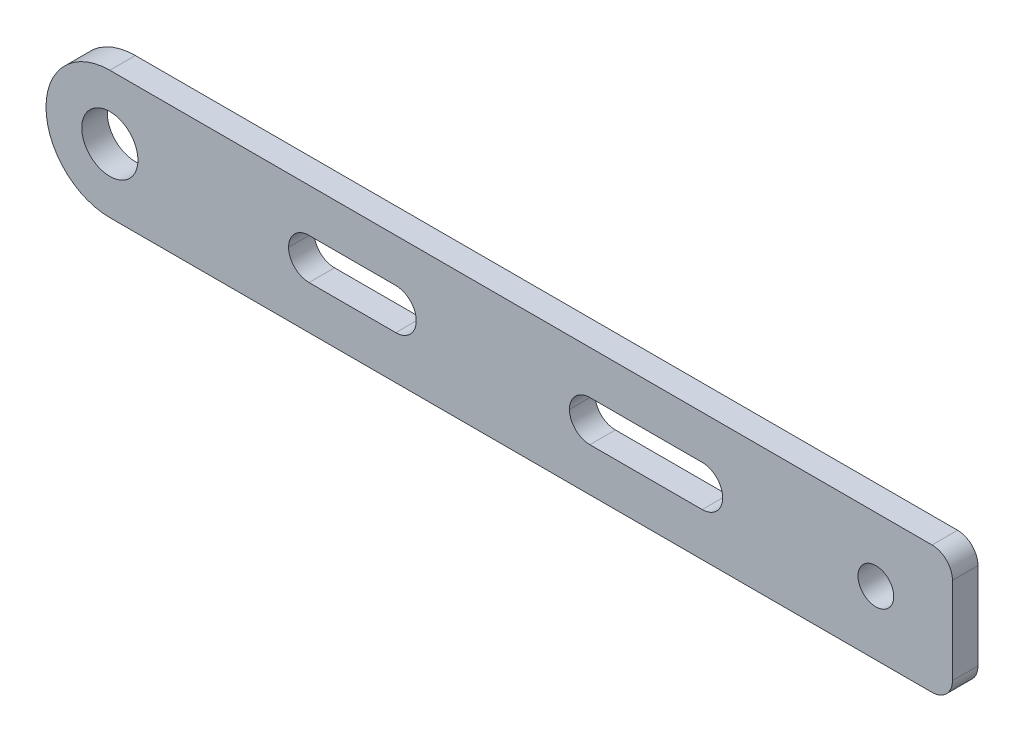
SolidWorks part; units mm, degrees
ref_plane "Front Plane" through (0, 0, 0) normal (0, 0, 1) x (1, 0, 0)
ref_plane "Top Plane" through (0, 0, 0) normal (0, 1, 0) x (1, 0, 0)
ref_plane "Right Plane" through (0, 0, 0) normal (1, 0, 0) x (0, 0, -1)
sketch "Sketch1" plane through (0, 0, 0) normal (0, 0, 1) x (1, 0, 0)
  line L1 (87.5, -12.5) -> (-77.5, -12.5)
  line L2 (87.5, -12.5) -> (87.5, 12.5)
  line L3 (87.5, 12.5) -> (-77.5, 12.5)
  line L5 (87.5, -12.5) -> (-87.5, 12.5) construction
  line L6 (87.5, 12.5) -> (-87.5, -12.5) construction
  circle A4 centre (-77.5, 0) radius 5.5
  circle A5 centre (72.5, 0) radius 3.5
  arc A13 (-77.5, 12.5) -> (-77.5, -12.5) centre (-77.5, 0) ccw
  point P0 (0, 0)
  point P6 (-65.4441, 5.7384)
  dimension "D3" = 12.5
  dimension "D6" = 11
  dimension "D7" = 7
  dimension "D1" = 150
  dimension "D2" = 25
  dimension "D4" = 72.5
  dimension "D5" = 12.5
  dimension "D8" = 15
  dimension "D9" = 12.5
  dimension "D10" = 12.5
extrude "Boss-Extrude1" add sketch "Sketch1" along normal blind 5
sketch "Sketch2" plane through (0, 0, 0) normal (0, 0, -1) x (-1, 0, 0)
  line L0 (-87.5, -12.5) -> (-87.5, 12.5) construction
  line L1 (-42.5, 4) -> (-12.5, 4)
  line L2 (-42.5, 4) -> (-42.5, -4)
  line L3 (-42.5, -4) -> (-12.5, -4)
  line L4 (-12.5, 4) -> (-12.5, -4)
  line L5 (17.5, 4) -> (42.5, 4)
  line L6 (17.5, 4) -> (17.5, -4)
  line L7 (17.5, -4) -> (42.5, -4)
  line L8 (42.5, 4) -> (42.5, -4)
  line L10 (-87.5, 12.5) -> (77.5, 12.5) construction
  line L11 (77.5, -12.5) -> (-87.5, -12.5) construction
  dimension "D1" = 45
  dimension "D2" = 25
  dimension "D3" = 30
  dimension "D4" = 30
  dimension "D5" = 8.5
  dimension "D6" = 8.5
  dimension "D7" = 8.5
  dimension "D8" = 8.5
extrude "Cut-Extrude1" cut sketch "Sketch2" against normal blind 10
fillet "Fillet1" radius 4 10 edges at (12.5, -4, 2.5) (42.5, -4, 2.5) (42.5, 4, 2.5) (12.5, 4, 2.5) (-42.5, -4, 2.5) (-17.5, -4, 2.5) (-17.5, 4, 2.5) (-42.5, 4, 2.5) (87.5, 12.5, 2.5) (87.5, -12.5, 2.5)
